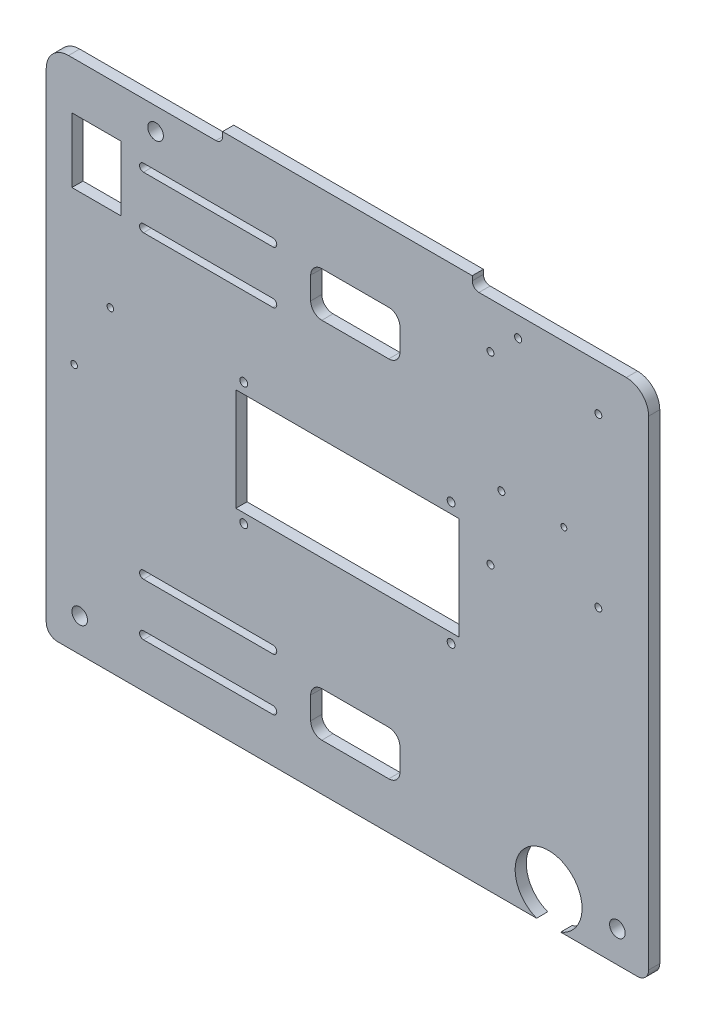
SolidWorks part; units mm, degrees
ref_plane "Front Plane" through (0, 0, 0) normal (0, 0, 1) x (1, 0, 0)
ref_plane "Top Plane" through (0, 0, 0) normal (0, 1, 0) x (1, 0, 0)
ref_plane "Right Plane" through (0, 0, 0) normal (1, 0, 0) x (0, 0, -1)
sketch "Sketch1" plane through (0, 0, 0) normal (0, 0, 1) x (1, 0, 0)
  line L1 (-135, 130) -> (135, 130)
  line L2 (-135, 130) -> (-135, -130)
  line L3 (-135, -130) -> (135, -130)
  line L4 (135, 130) -> (135, -130)
  line L5 (-135, 130) -> (135, -130) construction
  line L6 (-135, -130) -> (135, 130) construction
  point P0 (0, 0)
  dimension "D1" = 270
  dimension "D2" = 260
extrude "Boss-Extrude1" add sketch "Sketch1" along normal blind 5
sketch "Sketch2" plane through (0, 0, 0) normal (0, 0, -1) x (-1, 0, 0)
  circle A0 centre (120, -115) radius 3.5
  circle A1 centre (86, 90) radius 3.5
  circle A3 centre (-121, -116) radius 3.5
  dimension "D1" = 7
  dimension "D2" = 7
extrude "Cut-Extrude1" cut sketch "Sketch2" against normal through all
sketch "Sketch3" plane through (0, 0, 5) normal (0, 0, 1) x (1, 0, 0)
  circle A0 centre (90.1724, -116) radius 15
  dimension "D1" = 30
extrude "Cut-Extrude2" cut sketch "Sketch3" against normal through all
fillet "Fillet1" radius 5 4 edges at (135, -130, 2.5) (135, 130, 2.5) (-135, 130, 2.5) (-135, -130, 2.5)
sketch "Sketch4" plane through (0, 0, 0) normal (0, 0, -1) x (-1, 0, 0)
  line L0 (135, 100) -> (-135, 100)
  line L1 (135, 125) -> (135, -125) construction
  line L2 (-135, -125) -> (-135, 125) construction
  line L3 (95.6, 100) -> (90.2, 100)
  line L4 (-130, 130) -> (130, 130) construction
  line L5 (-135, 100) -> (-135, 125)
  line L6 (-130, 130) -> (130, 130)
  line L7 (135, 125) -> (135, 100)
  arc A0 (-130, 130) -> (-135, 125) centre (-130, 125) ccw construction
  arc A1 (135, 125) -> (130, 130) centre (130, 125) ccw construction
  arc A2 (-130, 130) -> (-135, 125) centre (-130, 125) ccw
  arc A3 (135, 125) -> (130, 130) centre (130, 125) ccw
  line M6 (-135, 125) -> (-135, -125)
  line M12 (135, -125) -> (135, 125)
  arc M13 (135, 125) -> (130, 130) centre (130, 125) ccw
  line M14 (130, 130) -> (-130, 130)
  arc M15 (-130, 130) -> (-135, 125) centre (-130, 125) ccw
extrude "Cut-Extrude3" cut sketch "Sketch4" against normal through all contours L0 M12 M13 M14 M15 M6 region at (0, 114.9816, 0)
sketch "Sketch5" plane through (0, 0, 0) normal (0, 0, -1) x (-1, 0, 0)
  circle A0 centre (-76.5, 91) radius 1.6
extrude "Cut-Extrude4" cut sketch "Sketch5" against normal through all
sketch "Sketch6" plane through (0, 0, 5) normal (0, 0, 1) x (1, 0, 0)
  line L0 (-135, 100) -> (135, 100) construction
  line L1 (-55.95, 100) -> (55.95, 100)
  line L2 (-55.95, 100) -> (-55.95, 105)
  line L3 (-55.95, 105) -> (55.95, 105)
  line L4 (55.95, 100) -> (55.95, 105)
  point P4 (0, 100)
  point P7 (0, 100)
  dimension "D1" = 111.9
  dimension "D2" = 5
extrude "Boss-Extrude2" add sketch "Sketch6" against normal up to surface (5 mm away) up to face at (74.9, 91, 0)
fillet "Fillet2" radius 10 2 edges at (135, 100, 2.5) (-135, 100, 2.5)
sketch "Sketch9" plane through (0, 0, 5) normal (0, 0, 1) x (1, 0, 0)
  line L1 (-123.5, 78.5) -> (-101.5, 78.5)
  line L2 (-123.5, 78.5) -> (-123.5, 49.5)
  line L3 (-123.5, 49.5) -> (-101.5, 49.5)
  line L4 (-101.5, 78.5) -> (-101.5, 49.5)
  line L5 (-123.5, 78.5) -> (-101.5, 49.5) construction
  line L6 (-123.5, 49.5) -> (-101.5, 78.5) construction
  point P0 (-112.5, 64)
extrude "Cut-Extrude5" cut sketch "Sketch9" against normal through all
sketch "Sketch10" plane through (0, 0, 0) normal (0, 0, -1) x (-1, 0, 0)
  circle A0 centre (-46.46, 12.46) radius 1.75
  circle A1 centre (46.46, 12.46) radius 1.75
  circle A2 centre (-46.46, -42.46) radius 1.75
  circle A3 centre (46.46, -42.46) radius 1.75
extrude "Cut-Extrude6" cut sketch "Sketch10" against normal through all
sketch "Sketch11" plane through (0, 0, 5) normal (0, 0, 1) x (1, 0, 0)
  line L1 (-50, 7.7465) -> (50, 7.7465)
  line L2 (-50, 7.7465) -> (-50, -38.2535)
  line L3 (-50, -38.2535) -> (50, -38.2535)
  line L4 (50, 7.7465) -> (50, -38.2535)
  line L5 (-50, 7.7465) -> (50, -38.2535) construction
  line L6 (-50, -38.2535) -> (50, 7.7465) construction
  point P0 (0, -15.2535)
  dimension "D1" = 46
  dimension "D2" = 100
extrude "Cut-Extrude7" cut sketch "Sketch11" against normal through all
sketch "Sketch12" plane through (0, 0, 5) normal (0, 0, 1) x (1, 0, 0)
  circle A0 centre (-106.25, 11.5) radius 1.475
  circle A1 centre (-122.5, -18.7) radius 1.475
  circle A2 centre (112.46, 4.3944) radius 1.5621
  circle A3 centre (64.1238, -3.0986) radius 1.5621
  circle A4 centre (69.0023, 27.9021) radius 1.5621
  circle A5 centre (97.0185, 27.9021) radius 1.3153
  circle A6 centre (112.46, 79.5276) radius 1.5621
  circle A7 centre (64.1238, 79.5276) radius 1.5621
extrude "Cut-Extrude8" cut sketch "Sketch12" against normal through all
sketch "Sketch13" plane through (0, 0, 0) normal (0, 0, -1) x (-1, 0, 0)
  line L0 (101.5, 49.5) -> (101.5, 78.5) construction
  line L3 (125, 100) -> (55.95, 100) construction
  line L6 (33.419, 73.25) -> (91.4088, 73.25) construction
  line L7 (33.419, 75) -> (91.4088, 75)
  line L8 (33.419, 71.5) -> (91.4088, 71.5)
  line L9 (33.419, 49.75) -> (91.4088, 49.75) construction
  line L10 (33.419, 51.5) -> (91.4088, 51.5)
  line L11 (33.419, 48) -> (91.4088, 48)
  line L12 (-135, -17.5) -> (135, -17.5) construction
  line L15 (-135, -125) -> (-135, 90) construction
  line L16 (-23.5308, 74) -> (16.4692, 74)
  line L17 (-23.5308, 74) -> (-23.5308, 54)
  line L18 (-23.5308, 54) -> (16.4692, 54)
  line L19 (16.4692, 74) -> (16.4692, 54)
  line L20 (-23.5308, 74) -> (16.4692, 54) construction
  line L21 (-23.5308, 54) -> (16.4692, 74) construction
  line L26 (135, 90) -> (135, -125) construction
  line L27 (-23.5308, -89) -> (16.4692, -109) construction
  line L28 (-23.5308, -109) -> (16.4692, -89) construction
  line L29 (16.4692, -109) -> (16.4692, -89)
  line L30 (-23.5308, -89) -> (16.4692, -89)
  line L31 (-23.5308, -109) -> (-23.5308, -89)
  line L32 (-23.5308, -109) -> (16.4692, -109)
  line L33 (33.419, -84.75) -> (91.4088, -84.75) construction
  line L34 (33.419, -86.5) -> (91.4088, -86.5)
  line L35 (33.419, -83) -> (91.4088, -83)
  line L36 (33.419, -108.25) -> (91.4088, -108.25) construction
  line L37 (33.419, -110) -> (91.4088, -110)
  line L38 (33.419, -106.5) -> (91.4088, -106.5)
  arc A4 (33.419, 75) -> (33.419, 71.5) centre (33.419, 73.25) ccw
  arc A5 (91.4088, 71.5) -> (91.4088, 75) centre (91.4088, 73.25) ccw
  arc A6 (33.419, 51.5) -> (33.419, 48) centre (33.419, 49.75) ccw
  arc A7 (91.4088, 48) -> (91.4088, 51.5) centre (91.4088, 49.75) ccw
  arc A10 (33.419, -86.5) -> (33.419, -83) centre (33.419, -84.75) cw
  arc A11 (91.4088, -83) -> (91.4088, -86.5) centre (91.4088, -84.75) cw
  arc A12 (33.419, -110) -> (33.419, -106.5) centre (33.419, -108.25) cw
  arc A13 (91.4088, -106.5) -> (91.4088, -110) centre (91.4088, -108.25) cw
  point P0 (16.4692, 64)
  point P3 (101.5, 64)
  point P14 (62.4139, 73.25)
  point P21 (62.4139, 49.75)
  point P30 (-3.5308, -99)
  point P33 (62.4139, -84.75)
  point P35 (-3.5308, 64)
  point P45 (62.4139, -108.25)
  dimension "D1" = 1.75
  dimension "D2" = 20
  dimension "D3" = 25
  dimension "D4" = 40
  dimension "D5" = 20
extrude "Cut-Extrude9" cut sketch "Sketch13" against normal through all
fillet "Fillet3" radius 3 2 edges at (55.95, 100, 2.5) (-55.95, 100, 2.5)
fillet "Fillet6" radius 5 4 edges at (-16.4692, 54, 2.5) (-16.4692, 74, 2.5) (23.5308, 54, 2.5) (23.5308, 74, 2.5)
fillet "Fillet7" radius 5 4 edges at (-16.4692, -109, 2.5) (-16.4692, -89, 2.5) (23.5308, -89, 2.5) (23.5308, -109, 2.5)
